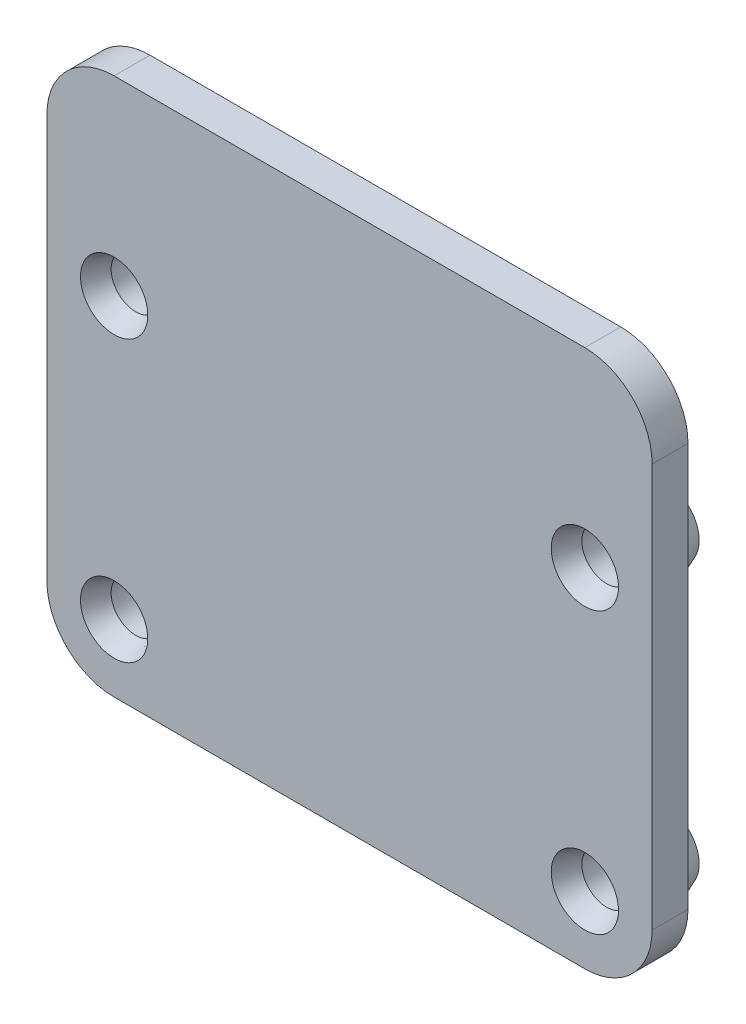
SolidWorks part; units mm, degrees
ref_plane "Front Plane" through (0, 0, 0) normal (0, 0, 1) x (1, 0, 0)
ref_plane "Top Plane" through (0, 0, 0) normal (0, 1, 0) x (1, 0, 0)
ref_plane "Right Plane" through (0, 0, 0) normal (1, 0, 0) x (0, 0, -1)
sketch "Sketch1" plane through (0, 0, 0) normal (0, 0, 1) x (1, 0, 0)
  line L0 (0, 13.48) -> (0, -10.52) construction
  line L1 (10.5, 13.48) -> (-10.5, 13.48)
  line L2 (13.5, 10.48) -> (13.5, -7.52)
  line L3 (10.5, -10.52) -> (-10.5, -10.52)
  line L4 (-13.5, 10.48) -> (-13.5, -7.52)
  arc A0 (-10.5, -10.52) -> (-13.5, -7.52) centre (-10.5, -7.52) cw
  arc A1 (-10.5, 13.48) -> (-13.5, 10.48) centre (-10.5, 10.48) ccw
  arc A2 (10.5, 13.48) -> (13.5, 10.48) centre (10.5, 10.48) cw
  arc A3 (13.5, -7.52) -> (10.5, -10.52) centre (10.5, -7.52) cw
  point P4 (10.5, 4.98)
  point P5 (10.5, -7.52)
  point P7 (-10.5, -7.52)
  point P9 (-10.5, 4.98)
  point P17 (-13.5, -10.52)
  point P20 (-13.5, 13.48)
  dimension "D4" = 3
  dimension "D1" = 3
  dimension "D2" = 3
  dimension "D3" = 24
extrude "Boss-Extrude1" add sketch "Sketch1" along normal blind 1.6
sketch "Sketch4" plane through (0, 0, 0) normal (0, 0, -1) x (-1, 0, 0)
  circle A0 centre (-10.5, 4.98) radius 2.3
  circle A1 centre (10.5, 4.98) radius 2.3
  circle A2 centre (10.5, -7.52) radius 2.3
  circle A3 centre (-10.5, -7.52) radius 2.3
  dimension "D1" = 4.6
extrude "Boss-Extrude2" add sketch "Sketch4" along normal blind 2
hole_wizard "M2 Clearance Hole1" positions "Sketch2" profile "Sketch3" hole size "M2" standard "ISO" end condition through all
sketch "Sketch2" plane through (0, 0, 1.6) normal (0, 0, 1) x (1, 0, 0)
  point P0 (10.5, 4.98)
  point P2 (10.5, -7.52)
  point P4 (-10.5, -7.52)
  point P6 (-10.5, 4.98)
sketch "Sketch3" plane through (10.5, 4.98, 1.6) normal (1, 0, 0) x (0, -1, 0)
  line L0 (0, 0) -> (0, 3.6)
  line L1 (0, 3.6) -> (1.1, 3.6)
  line L2 (1.1, 3.6) -> (1.1, 0.9657)
  line L3 (1.1, 0.9657) -> (1.5, 0)
  line L5 (1.5, 0) -> (0, 0)
  line L6 (-1.1, 0.9657) -> (-1.5, 0) construction
  line L11 (0, -6.35) -> (0, 107.95) construction
  dimension "Thru Hole Dia." = 2.2
  dimension "Thru Hole Depth" = 3.6
  dimension "Near C'Sink Dia." = 3
  dimension "Near C'Sink Angle" = 45
chamfer "Chamfer1" distance 2 distance2 0.8 4 edges at (-12.8, -7.52, -2) (-12.8, 4.98, -2) (8.2, 4.98, -2) (8.2, -7.52, -2) first distance on face at (-12.8, -7.52, -2) first distance on face at (-12.8, 4.98, -2) first distance on face at (8.2, 4.98, -2) first distance on face at (8.2, -7.52, -2)
